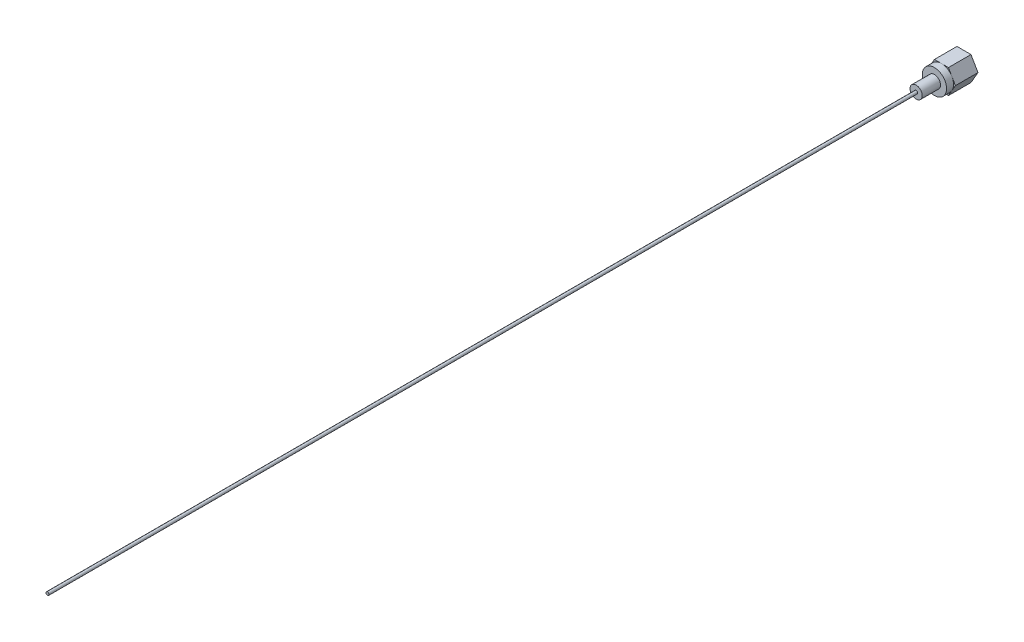
SolidWorks part; units mm, degrees
ref_plane "Alzado" through (0, 0, 0) normal (0, 0, 1) x (1, 0, 0)
ref_plane "Planta" through (0, 0, 0) normal (0, 1, 0) x (1, 0, 0)
ref_plane "Vista lateral" through (0, 0, 0) normal (1, 0, 0) x (0, 0, -1)
sketch "Sketch1" plane through (0, 0, 0) normal (0, 0, 1) x (1, 0, 0)
  line L1 (2.3, -3.9837) -> (4.6, 0)
  line L2 (4.6, 0) -> (2.3, 3.9837)
  line L3 (2.3, 3.9837) -> (-2.3, 3.9837)
  line L4 (-2.3, 3.9837) -> (-4.6, 0)
  line L5 (-4.6, 0) -> (-2.3, -3.9837)
  line L6 (-2.3, -3.9837) -> (2.3, -3.9837)
  circle A0 centre (0, 0) radius 3.9837 construction
  dimension "D1" = 4.6
extrude "Boss-Extrude1" add sketch "Sketch1" along normal blind 7.4
sketch "Sketch2" plane through (0, 0, 7.4) normal (0, 0, 1) x (1, 0, 0)
  line L0 (-2.3, 3.9837) -> (-4.6, 0) construction
  circle A0 centre (0, 0) radius 3.9837
extrude "Boss-Extrude2" add sketch "Sketch2" along normal blind 2.3
sketch "Sketch3" plane through (0, 0, 9.7) normal (0, 0, 1) x (1, 0, 0)
  circle A0 centre (0, 0) radius 2
  dimension "D1" = 4
extrude "Boss-Extrude3" add sketch "Sketch3" along normal blind 6
sketch "Sketch4" plane through (0, 0, 15.7) normal (0, 0, 1) x (1, 0, 0)
  circle A0 centre (0, 0) radius 0.5
  dimension "D1" = 1
extrude "Boss-Extrude4" add sketch "Sketch4" along normal blind 285
